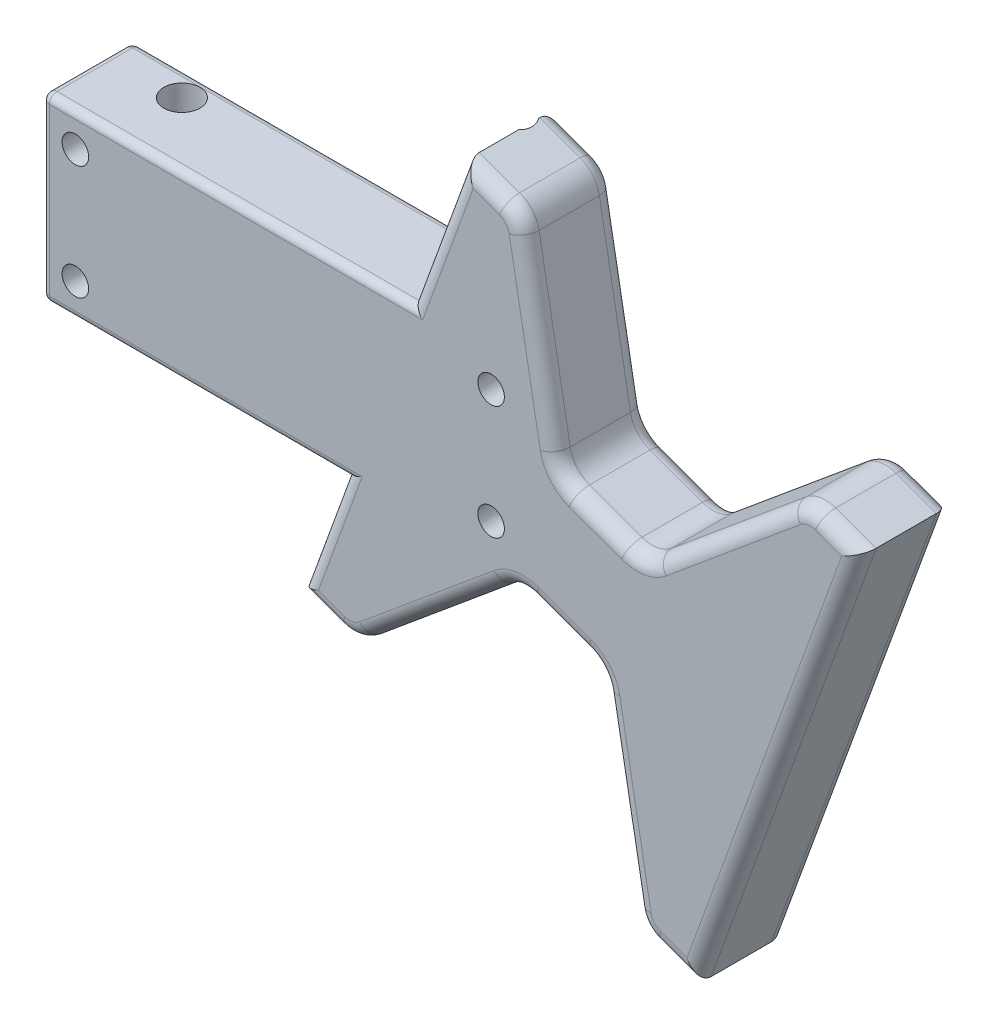
SolidWorks part; units mm, degrees
ref_plane "Front Plane" through (0, 0, 0) normal (0, 0, 1) x (1, 0, 0)
ref_plane "Top Plane" through (0, 0, 0) normal (0, 1, 0) x (1, 0, 0)
ref_plane "Right Plane" through (0, 0, 0) normal (1, 0, 0) x (0, 0, -1)
sketch "Sketch1" plane through (0, 0, 0) normal (0, 0, 1) x (1, 0, 0)
  line L1 (-25.4, 9.525) -> (25.4, 9.525)
  line L2 (-25.4, 9.525) -> (-25.4, -9.525)
  line L3 (-25.4, -9.525) -> (25.4, -9.525)
  line L4 (25.4, 9.525) -> (25.4, -9.525)
  line L5 (-25.4, 9.525) -> (25.4, -9.525) construction
  line L6 (-25.4, -9.525) -> (25.4, 9.525) construction
  point P0 (0, 0)
  dimension "D1" = 50.8
  dimension "D2" = 19.05
extrude "Boss-Extrude1" add sketch "Sketch1" along normal blind 9.525
sketch "Sketch11" plane through (0, 0, 9.525) normal (0, 0, 1) x (1, 0, 0)
  line L0 (19.05, 25.4) -> (1.6754, -22.3364)
  line L1 (1.6754, -22.3364) -> (43.4447, -37.5392)
  line L2 (43.4447, -37.5392) -> (60.8193, 10.1972)
  line L3 (60.8193, 10.1972) -> (19.05, 25.4)
  line L4 (-25.4, -9.525) -> (25.4, -9.525) construction
  dimension "D1" = 50.8
  dimension "D2" = 44.45
  dimension "D3" = 70
  dimension "D4" = 19.05
  dimension "D5" = 25.4
extrude "Boss-Extrude4" add sketch "Sketch11" against normal up to surface (9.525 mm away) up to face at (0, 0, 0)
sketch "Sketch12" plane through (0, 0, 9.525) normal (0, 0, 1) x (1, 0, 0)
  line L0 (25.017, 23.2282) -> (28.9439, 1.5263)
  line L1 (60.8193, 10.1972) -> (19.05, 25.4) construction
  line L3 (54.8523, 12.369) -> (25.017, 23.2282)
  line L4 (52.132, -13.671) -> (11.6105, 1.0777) construction
  line L5 (43.4447, -37.5392) -> (60.8193, 10.1972) construction
  line L13 (28.9439, 1.5263) -> (37.8945, -1.7314)
  line L14 (37.8945, -1.7314) -> (54.8523, 12.369)
  line L15 (37.4777, -35.3674) -> (7.6424, -24.5082)
  line L16 (7.6424, -24.5082) -> (24.6002, -10.4078)
  line L17 (24.6002, -10.4078) -> (33.5508, -13.6655)
  line L18 (33.5508, -13.6655) -> (37.4777, -35.3674)
  point P5 (27.9948, 1.8094)
  dimension "D1" = 6.35
  dimension "D2" = 6.35
  dimension "D3" = 9.525
  dimension "D4" = 6.35
extrude "Cut-Extrude5" cut sketch "Sketch12" against normal through all
sketch "Sketch2" plane through (0, 0, 9.525) normal (0, 0, 1) x (1, 0, 0)
  line L0 (-21.8821, 6.0071) -> (-21.8821, -6.0071) construction
  line L1 (-21.8821, 6.0071) -> (-25.4, 6.0071) construction
  line L2 (-25.4, 9.525) -> (-25.4, -9.525) construction
  line L3 (-21.8821, 6.0071) -> (-21.8821, 9.525) construction
  line L4 (13.272, 9.525) -> (-25.4, 9.525) construction
  line L5 (0, -9.525) -> (0, 9.525) construction
  line L6 (13.272, 9.525) -> (-25.4, 9.525) construction
  line L7 (-25.4, -9.525) -> (6.3383, -9.525) construction
  circle A0 centre (-21.8821, 6.0071) radius 1.397
  circle A1 centre (-21.8821, -6.0071) radius 1.397
  circle A2 centre (21.8821, -6.0071) radius 1.397
  circle A3 centre (21.8821, 6.0071) radius 1.397
  point P4 (-21.8821, 0)
  point P15 (0, 0)
  point P19 (-25.4, 6.1722)
  point P20 (-18.8722, 12.7)
  point P23 (18.8722, -6.1722)
  point P24 (-18.8722, -6.1722)
  point P25 (0, 12.7)
  point P26 (-18.8722, -6.1722)
  point P27 (0, 0)
  point P28 (-18.8722, -6.1722)
  point P29 (0, 12.7)
  point P30 (0, -12.7)
  dimension "D1" = 12.0142
  dimension "D2" = 2.794
  dimension "D3" = 2.794
  dimension "D4" = 25.4
extrude "Cut-Extrude1" cut sketch "Sketch2" against normal through all
sketch "Sketch4" plane through (0, 9.525, 0) normal (0, 1, 0) x (1, 0, 0)
  line L1 (0, 0) -> (0, -9.525) construction
  line L2 (13.272, -9.525) -> (-25.4, -9.525) construction
  line L3 (-25.4, -9.525) -> (-25.4, 0) construction
  circle A2 centre (-17.4625, -2.7305) radius 1.905
  circle A3 centre (17.4625, -2.7305) radius 1.905
  point P6 (-19.8755, -3.3536)
  dimension "D1" = 25.4
  dimension "D4" = 3.81
  dimension "D2" = 7.9375
  dimension "D3" = 6.7945
extrude "Cut-Extrude2" cut sketch "Sketch4" against normal through all both and the other way through all
sketch "Sketch5" plane through (0, 9.525, 0) normal (0, 1, 0) x (1, 0, 0)
  line L0 (14.2875, -2.7305) -> (14.2875, 0)
  line L1 (13.272, 0) -> (-25.4, 0) construction
  line L2 (20.6375, -2.7305) -> (20.6375, 0)
  line L3 (14.2875, 0) -> (20.6375, 0)
  arc A1 (14.2875, -2.7305) -> (20.6375, -2.7305) centre (17.4625, -2.7305) ccw
  arc A2 (19.05, -1.6775) -> (19.05, -3.7835) centre (17.4625, -2.7305) ccw construction
  dimension "D1" = 3.175
extrude "Cut-Extrude3" cut sketch "Sketch5" against normal blind 3.175 from offset 9.525 offset against normal yes
sketch "Sketch6" plane through (0, 9.525, 0) normal (0, 1, 0) x (1, 0, 0)
  line L0 (-14.2875, -2.7305) -> (-14.2875, 0)
  line L1 (13.272, 0) -> (-25.4, 0) construction
  line L2 (-20.6375, -2.7305) -> (-20.6375, 0)
  line L3 (-20.6375, 0) -> (-14.2875, 0)
  arc A0 (-20.6375, -2.7305) -> (-14.2875, -2.7305) centre (-17.4625, -2.7305) ccw
  dimension "D1" = 6.35
extrude "Cut-Extrude4" cut sketch "Sketch6" against normal blind 3.175 from offset 6.35 offset against normal yes
sketch "Sketch9" plane through (0, 0, 0) normal (0, 0, -1) x (-1, 0, 0)
  circle A0 centre (-21.8821, 6.0071) radius 1.397
  circle A1 centre (-21.8821, 6.0071) radius 2.6987
  circle A2 centre (-21.8821, 6.0071) radius 1.397 construction
  circle A3 centre (21.8821, -6.0071) radius 1.397
  circle A4 centre (21.8821, -6.0071) radius 2.6987
  circle A5 centre (21.8821, -6.0071) radius 1.397 construction
  dimension "D1" = 5.3975
  dimension "D2" = 5.3975
extrude "Boss-Extrude2" add sketch "Sketch9" along normal blind 2.667
chamfer "Chamfer1" distance 0.635 angle 45 2 edges at (-24.5808, -6.0071, -2.667) (19.1833, 6.0071, -2.667)
fillet "Fillet2" radius 3.175 8 edges at (7.6424, -24.5082, 4.7625) (33.5508, -13.6655, 4.7625) (24.6002, -10.4078, 4.7625) (37.4777, -35.3674, 4.7625) (54.8523, 12.369, 4.7625) (37.8945, -1.7314, 4.7625) (28.9439, 1.5263, 4.7625) (25.017, 23.2282, 4.7625)
fillet "Fillet4" radius 1.5875 42 edges at (21.1767, 24.6259, 0) (24.6451, 22.9147, 0) (26.9805, 12.3773, 0) (58.6926, 10.9713, 0) (54.9357, 11.8898, 0) (46.3734, 5.3188, 0) (37.8111, -1.2522, 0) (33.4192, -0.1025, 0) (41.318, -36.7651, 0) (37.8496, -35.0538, 0) (3.8021, -23.1104, 0) (7.559, -24.029, 0) (16.1213, -17.458, 0) (24.6836, -10.887, 0) (29.0755, -12.0366, 0) (33.1789, -13.979, 0) (21.1767, 24.6259, 9.525) (24.6451, 22.9147, 9.525) (26.9805, 12.3773, 9.525) (29.3158, 1.8398, 9.525) (58.6926, 10.9713, 9.525) (54.9357, 11.8898, 9.525) (46.3734, 5.3188, 9.525) (37.8111, -1.2522, 9.525) (41.318, -36.7651, 9.525) (37.8496, -35.0538, 9.525) (35.5142, -24.5164, 9.525) (33.1789, -13.979, 9.525) (29.0755, -12.0366, 9.525) (24.6836, -10.887, 9.525) (3.8021, -23.1104, 9.525) (7.559, -24.029, 9.525) (4.0069, -15.9307, 9.525) (4.0069, -15.9307, 0) (16.161, 17.4625, 9.525) (16.161, 17.4625, 0) (29.3158, 1.8398, 0) (35.5142, -24.5164, 0) (52.132, -13.671, 0) (33.4192, -0.1025, 9.525) (52.132, -13.671, 9.525) (16.1213, -17.458, 9.525)
fillet "Fillet5" radius 0.7937 8 edges at (-25.4, 9.525, 4.7625) (-25.4, -9.525, 4.7625) (-5.2193, 9.525, 9.525) (-8.6861, -9.525, 9.525) (-25.4, 0, 9.525) (-25.4, 0, 0) (-5.2193, 9.525, 0) (-8.6861, -9.525, 0)
